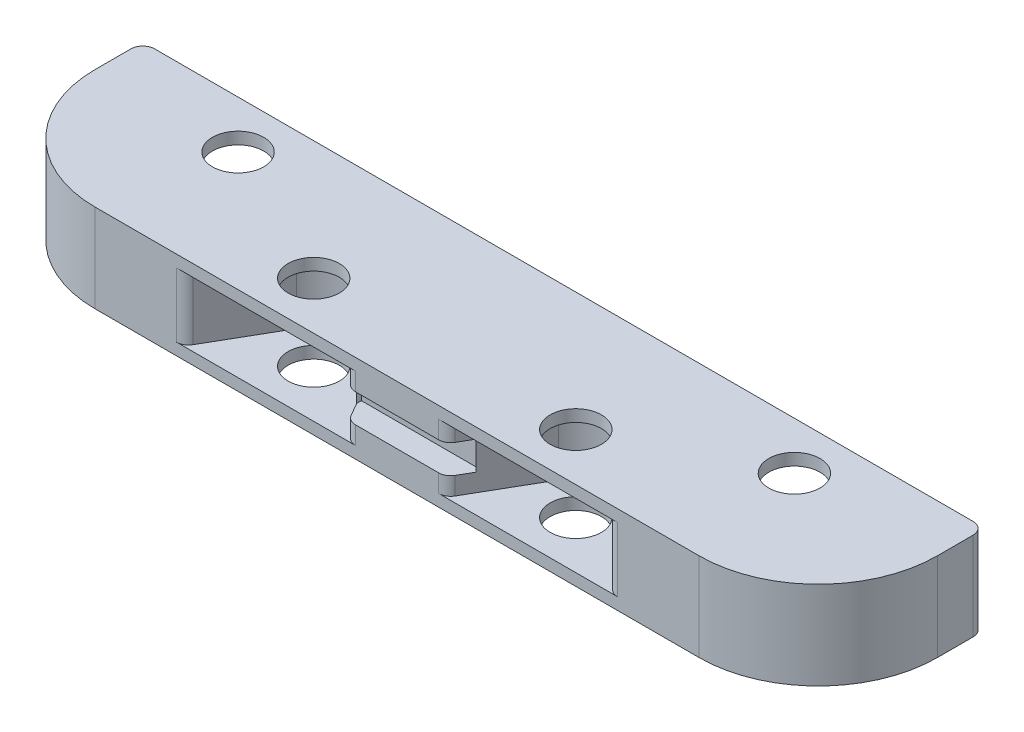
SolidWorks part; units mm, degrees
ref_plane "Front Plane" through (0, 0, 0) normal (0, 0, 1) x (1, 0, 0)
ref_plane "Top Plane" through (0, 0, 0) normal (0, 1, 0) x (1, 0, 0)
ref_plane "Right Plane" through (0, 0, 0) normal (1, 0, 0) x (0, 0, -1)
sketch "Sketch2" plane through (0, 0, 0) normal (0, 1, 0) x (1, 0, 0)
  line L0 (0, 4) -> (35.35, 4)
  line L1 (35.35, 4) -> (35.35, 0)
  line L3 (11, -10) -> (0, -10)
  line L4 (0, -10) -> (0, 4)
  line L5 (7.5359, -4) -> (4.0718, -10)
  line L6 (11, -10) -> (25.35, -10)
  line L7 (14.35, 0) -> (14.35, 4)
  line L8 (32.35, 0) -> (32.35, 4)
  line L9 (16.85, 0) -> (16.85, 17.1334) construction
  line L10 (14.4641, -4) -> (17.9282, -10)
  circle A0 centre (23.35, 0) radius 2.15
  circle A1 centre (11, -6) radius 2.15
  circle A2 centre (23.35, 0) radius 9
  circle A3 centre (11, -6) radius 4
  circle A4 centre (23.35, 0) radius 6.5 construction
  arc A5 (35.35, 0) -> (25.35, -10) centre (25.35, 0) cw
  dimension "D2" = 4.3
  dimension "D3" = 6
  dimension "D9" = 2.5
  dimension "D10" = 8
  dimension "D12" = 13
  dimension "D8" = 4
  dimension "D4" = 11
  dimension "D5" = 12
  dimension "D6" = 4
  dimension "D7" = 4
  dimension "D11" = 60
  dimension "D13" = 23.35
extrude "Boss-Extrude6" add sketch "Sketch2" along normal blind 2.7 contours A5 L1 L0 L8 A2 L7 L4 L3 L5 A3 region at (12.823, 0, 2.4132)
extrude "Boss-Extrude7" add sketch "Sketch2<4>" along normal blind 1 from surface contours A5 L1 L0 L8 A2 L7 L4 L3 L5 A3 L10 L6 | A3 L5 L3 | A3 A1 | A3 L6 L10 | A2 L0 A0 | A2 L0 L7 | A2 L8 L0 region at (12.823, 0, 2.4132) region at (14.6286, 0, -3.0107) region at (23.35, 0, -3.778) region at (6.6195, 0, 8.5291) region at (32.0714, 0, -3.0107) region at (15.3805, 0, 8.5291) region at (7.6339, 0, 7.9434) starting at face at (18.117, 2.7, 3.1593)
sketch "Sketch2<4>" plane through (0, 0, 0) normal (0, 1, 0) x (1, 0, 0) same geometry as "Sketch2"
mirror "Mirror1" about plane through (0, 0, 0) normal (0, 1, 0) of bodies 103
mirror "Mirror2" about plane through (0, 0, 0) normal (1, 0, 0) of bodies 104
fillet "Fillet1" radius 1 10 edges at (-4.0718, 0, 10) (4.0718, 0, 10) (35.35, 0, -4) (-35.35, 0, -4) (-14.35, 0, -4) (-32.35, 0, -4) (32.35, 0, -4) (14.35, 0, -4) (17.9282, 0, 10) (-17.9282, 0, 10)
sketch "Sketch3" plane through (0, 0, 0) normal (0, 0, 1) x (1, 0, 0)
  line L1 (-5, 1.2) -> (5, 1.2)
  line L2 (-5, 1.2) -> (-5, -1.2)
  line L3 (-5, -1.2) -> (5, -1.2)
  line L4 (5, 1.2) -> (5, -1.2)
  point P4 (5, 0)
  point P5 (0, 1.2)
  dimension "D1" = 2.4
  dimension "D2" = 10
extrude "Cut-Extrude1" cut sketch "Sketch3" against normal blind 2 from surface starting at face at (0, 0, 10)
